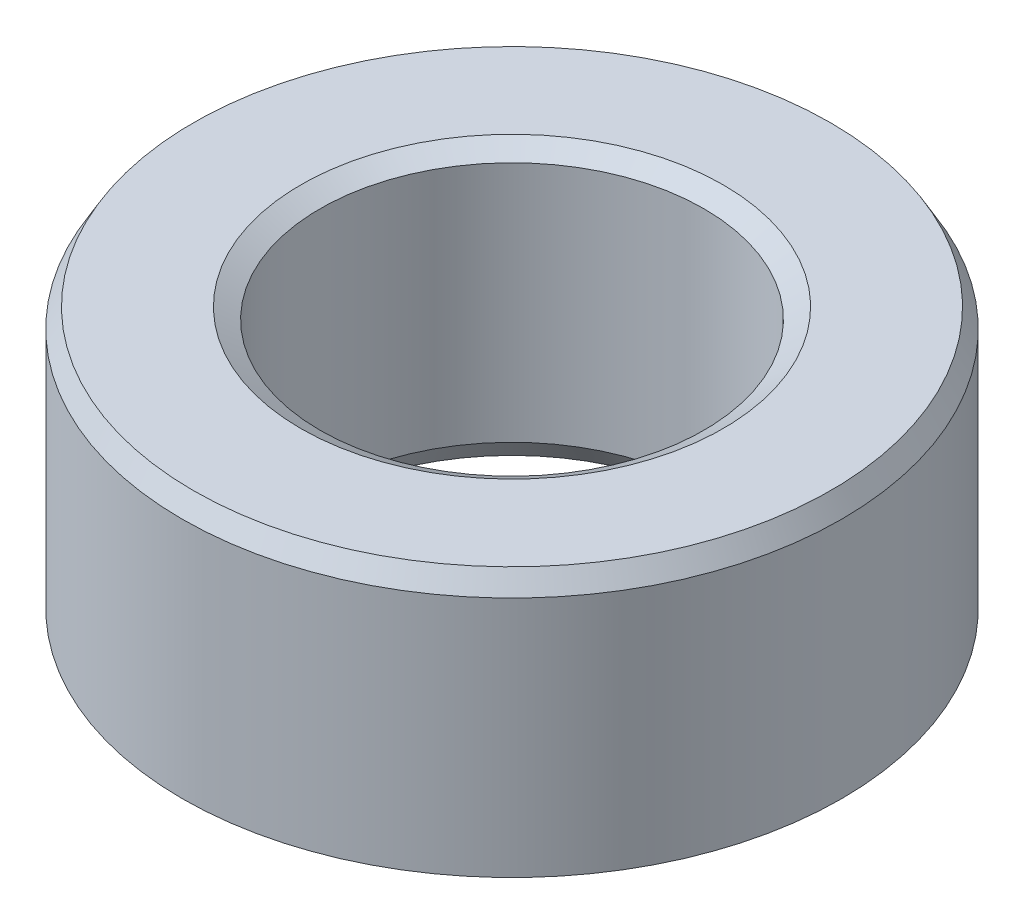
SolidWorks part; units mm, degrees
ref_plane "Front Plane" through (0, 0, 0) normal (0, 0, 1) x (1, 0, 0)
ref_plane "Top Plane" through (0, 0, 0) normal (0, 1, 0) x (1, 0, 0)
ref_plane "Right Plane" through (0, 0, 0) normal (1, 0, 0) x (0, 0, -1)
sketch "Sketch1" plane through (0, 0, 0) normal (0, 1, 0) x (1, 0, 0)
  circle A0 centre (0, 0) radius 50
  dimension "SLEEVE_OD" = 100
extrude "Boss-Extrude1" add sketch "Sketch1" along normal blind 41.3058
sketch "Sketch2" plane through (0, 0, 0) normal (0, 1, 0) x (1, 0, 0)
  circle A0 centre (0, 0) radius 29.1086
  dimension "BORE_D" = 58.2172
extrude "Cut-Extrude1" cut sketch "Sketch2" along normal through all
chamfer "Chamfer1" distance 2.9143 angle 30 4 edges at (0, 41.3058, 29.1086) (0, 0, 29.1086) (0, 0, 50) (0, 41.3058, 50) first distance on face at (0, 41.3058, 29.1086) first distance on face at (0, 0, 29.1086) first distance on face at (0, 41.3058, 50)
